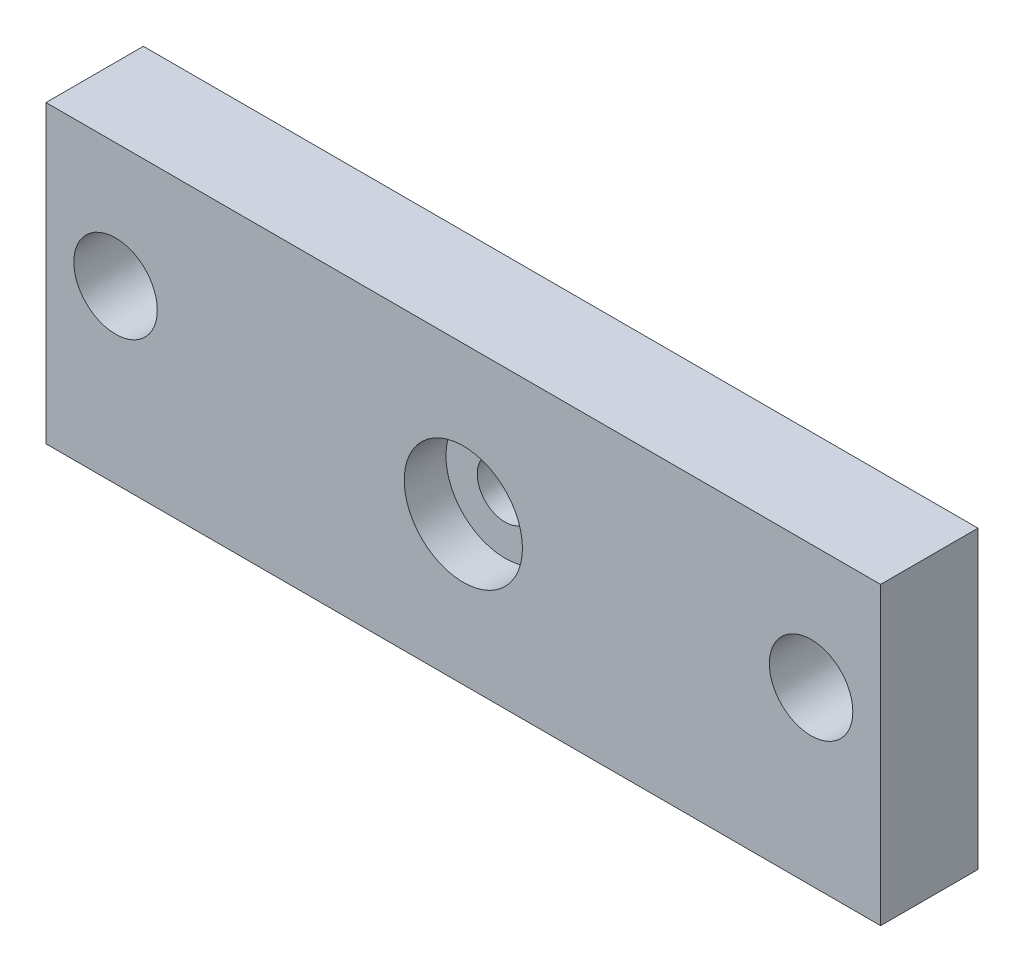
SolidWorks part; units mm, degrees
ref_plane "Front Plane" through (0, 0, 0) normal (0, 0, 1) x (1, 0, 0)
ref_plane "Top Plane" through (0, 0, 0) normal (0, 1, 0) x (1, 0, 0)
ref_plane "Right Plane" through (0, 0, 0) normal (1, 0, 0) x (0, 0, -1)
sketch "Sketch1" plane through (0, 0, 0) normal (0, 0, 1) x (1, 0, 0)
  line L1 (-60, -21.25) -> (60, -21.25)
  line L2 (-60, -21.25) -> (-60, 21.25)
  line L3 (-60, 21.25) -> (60, 21.25)
  line L4 (60, -21.25) -> (60, 21.25)
  line L5 (-60, -21.25) -> (60, 21.25) construction
  line L6 (-60, 21.25) -> (60, -21.25) construction
  point P0 (0, 0)
  dimension "D1" = 120
  dimension "D2" = 42.5
extrude "Boss-Extrude1" add sketch "Sketch1" along normal mid plane 14
sketch "Sketch2" plane through (0, 0, 7) normal (0, 0, 1) x (1, 0, 0)
  circle A0 centre (0, 0) radius 8.5
  dimension "D1" = 17
extrude "Cut-Extrude1" cut sketch "Sketch2" against normal blind 6
sketch "Sketch3" plane through (0, 0, 1) normal (0, 0, 1) x (1, 0, 0)
  circle A0 centre (0, 0) radius 4
  dimension "D1" = 8
extrude "Cut-Extrude2" cut sketch "Sketch3" against normal through all
sketch "Sketch5" plane through (0, 0, 7) normal (0, 0, 1) x (1, 0, 0)
  line L0 (-40.6477, 3.4) -> (36.4799, 3.4) construction
  circle A0 centre (-50, 3.4) radius 6
  circle A1 centre (50, 3.4) radius 6
  dimension "D1" = 12
  dimension "D2" = 12
  dimension "D4" = 50
  dimension "D3" = 50
  dimension "D5" = 3.4
extrude "Cut-Extrude4" cut sketch "Sketch5" against normal through all
sketch "Sketch6" plane through (0, -21.25, 0) normal (0, -1, 0) x (1, 0, 0)
  line L0 (-60, 0) -> (60, 0) construction
  line L1 (-60, 7) -> (-60, -7) construction
  line L2 (60, 7) -> (60, -7) construction
  circle A0 centre (-50, 0) radius 2.5
  circle A1 centre (-25, 0) radius 2.5
  circle A2 centre (25, 0) radius 2.5
  circle A3 centre (50, 0) radius 2.5
  circle A4 centre (-37.5, 0) radius 1.25
  circle A5 centre (37.5, 0) radius 1.25
  dimension "D1" = 5
  dimension "D2" = 5
  dimension "D3" = 5
  dimension "D4" = 5
  dimension "D5" = 10
  dimension "D9" = 2.5
  dimension "D10" = 2.5
  dimension "D11" = 22.5
  dimension "D12" = 22.5
  dimension "D6" = 35
  dimension "D7" = 10
  dimension "D8" = 35
extrude "Cut-Extrude5" cut sketch "Sketch6" against normal blind 10
